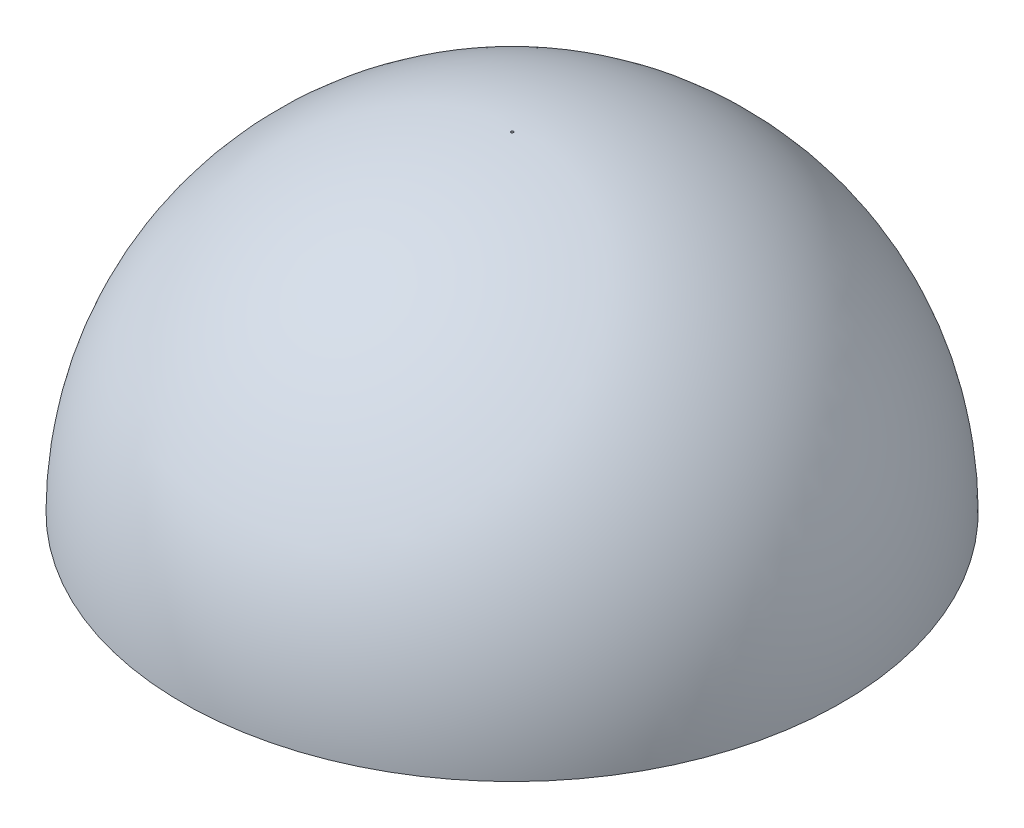
SolidWorks part; units mm, degrees
ref_plane "Front Plane" through (0, 0, 0) normal (0, 0, 1) x (1, 0, 0)
ref_plane "Top Plane" through (0, 0, 0) normal (0, 1, 0) x (1, 0, 0)
ref_plane "Right Plane" through (0, 0, 0) normal (1, 0, 0) x (0, 0, -1)
sketch "Sketch1" plane through (0, 0, 0) normal (0, 0, 1) x (1, 0, 0)
  line L0 (0, 294.386) -> (0, 298.45)
  line L1 (-294.386, 0) -> (-298.45, 0)
  line L2 (0, 0) -> (0, 294.386) construction
  circle A0 centre (0, 0) radius 298.45
  circle A1 centre (0, 0) radius 294.386
  dimension "D1" = 596.9
  dimension "D2" = 588.772
revolve "Revolve1" add sketch "Sketch1" angle 360 about L2 region at (-208.4608, 208.4608, 0)
sketch "Sketch2" plane through (-482.9313, -388.2515, 69.1995) normal (0, 1, 0) x (0.519, 0, -0.8547)
  circle A0 centre (309.812, -376.8657) radius 1.143
  dimension "D1" = 2.286
extrude "Cut-Extrude1" cut sketch "Sketch2" along normal blind 883.412
